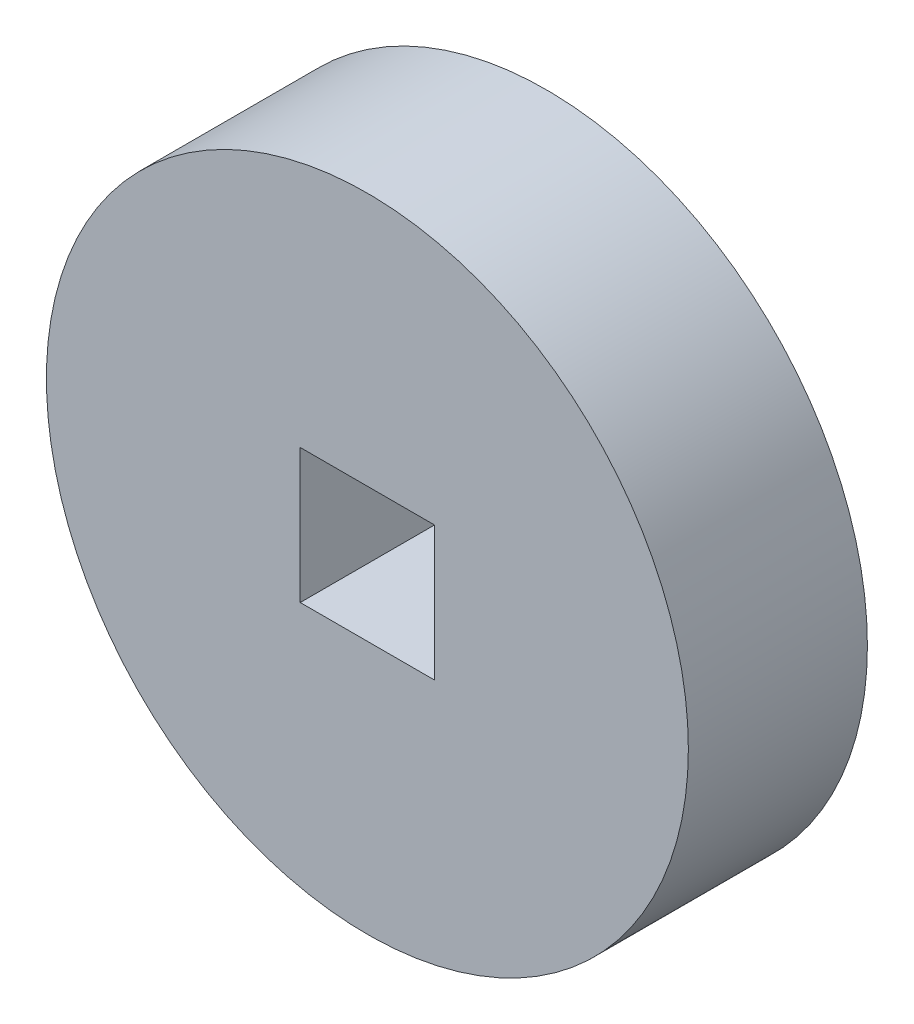
SolidWorks part; units mm, degrees
ref_plane "前视基准面" through (0, 0, 0) normal (0, 0, 1) x (1, 0, 0)
ref_plane "上视基准面" through (0, 0, 0) normal (0, 1, 0) x (1, 0, 0)
ref_plane "右视基准面" through (0, 0, 0) normal (1, 0, 0) x (0, 0, -1)
other "Configuration Table"
sketch "草图1" plane through (0, 0, 0) normal (0, 0, 1) x (1, 0, 0)
  line L1 (-1.5, -1.5) -> (1.5, -1.5)
  line L2 (-1.5, -1.5) -> (-1.5, 1.5)
  line L3 (-1.5, 1.5) -> (1.5, 1.5)
  line L4 (1.5, -1.5) -> (1.5, 1.5)
  line L5 (0, 1.5) -> (0, -1.5) construction
  line L6 (-1.5, 0) -> (1.5, 0) construction
  circle A0 centre (0, 0) radius 7.1707
  dimension "D1" = 3
  dimension "D2" = 3
extrude "凸台-拉伸1" add sketch "草图1" along normal blind 4
